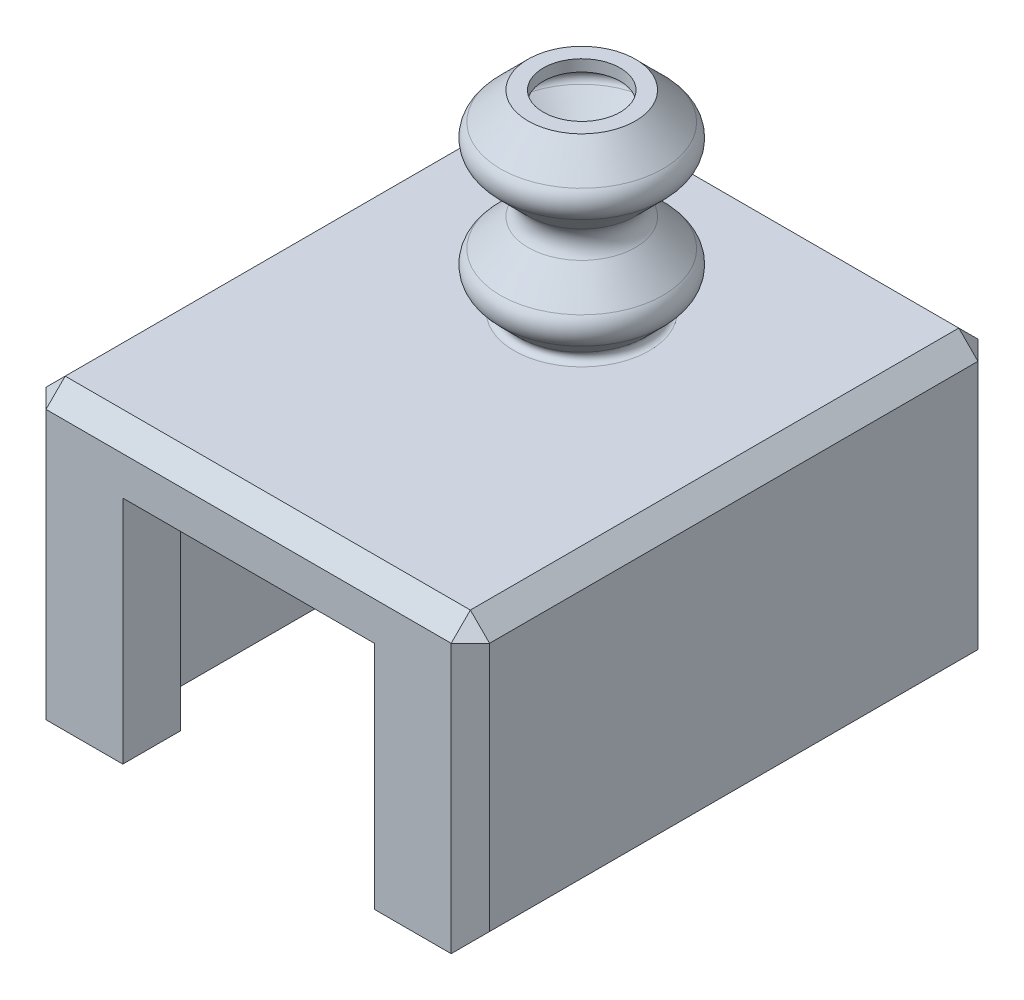
SolidWorks part; units mm, degrees
ref_plane "Front Plane" through (0, 0, 0) normal (0, 0, 1) x (1, 0, 0)
ref_plane "Top Plane" through (0, 0, 0) normal (0, 1, 0) x (1, 0, 0)
ref_plane "Right Plane" through (0, 0, 0) normal (1, 0, 0) x (0, 0, -1)
ref_axis "X Axis" through (-88.99, 0, 0) along (1, 0, 0)
ref_axis "Y Axis" through (0, 55, 0) along (0, -1, 0)
ref_axis "Z Axis" through (0, 0, -88.99) along (0, 0, 1)
sketch "Sketch1" plane through (0, 0, 0) normal (0, 0, 1) x (1, 0, 0)
  line L0 (0, 0) -> (2.7929, 0)
  line L1 (4.2322, 2.8536) -> (2.7929, 4.2929)
  line L2 (2.7929, 5.7071) -> (4.2322, 7.1464)
  line L3 (2.7929, 10) -> (0, 10)
  line L4 (0, 10) -> (0, 0) construction
  line L9 (0, 10) -> (0, 9.4)
  line L10 (0, 0.6) -> (0, 0)
  line L16 (4.2322, 8.5607) -> (2.7929, 10)
  line L17 (4.2322, 1.4393) -> (2.7929, 0)
  line L18 (3.5, 5) -> (0, 5) construction
  line L19 (0, 0.6) -> (2.5444, 0.6)
  line L20 (3.808, 1.8636) -> (2.5444, 0.6)
  line L21 (3.808, 2.4293) -> (2.3686, 3.8686)
  line L22 (2.3686, 6.1314) -> (3.808, 7.5707)
  line L23 (3.808, 8.1364) -> (2.5444, 9.4)
  line L24 (2.5444, 9.4) -> (0, 9.4)
  arc A0 (2.7929, 5.7071) -> (2.7929, 4.2929) centre (3.5, 5) ccw
  arc A1 (4.2322, 1.4393) -> (4.2322, 2.8536) centre (3.5251, 2.1464) ccw
  arc A2 (4.2322, 7.1464) -> (4.2322, 8.5607) centre (3.5251, 7.8536) ccw
  arc A3 (3.808, 1.8636) -> (3.808, 2.4293) centre (3.5251, 2.1464) ccw
  arc A4 (2.3686, 6.1314) -> (2.3686, 3.8686) centre (3.5, 5) ccw
  arc A5 (3.808, 7.5707) -> (3.808, 8.1364) centre (3.5251, 7.8536) ccw
  point P1 (2.7929, 5.7071)
  point P5 (2.7929, 4.2929)
  point P14 (2.7929, 4.2929)
  point P15 (2.7929, 4.2929)
  point P21 (0, 0)
  point P22 (0, 0)
  dimension "D3" = 1
  dimension "D4" = 1.9
  dimension "D1" = 5
  dimension "D2" = 10
  dimension "D5" = 0.6
revolve "Revolve1" add sketch "Sketch1" angle 360 about L4 region at (0.1098, 0.3, 0)
sketch "Sketch2" plane through (0, 10, 0) normal (0, 1, 0) x (1, 0, 0)
  circle A0 centre (0, 0) radius 2
  dimension "D1" = 4
extrude "Cut-Extrude1" cut sketch "Sketch2" against normal up to next
sketch "Sketch3" plane through (0, 0, 0) normal (0, -1, 0) x (1, 0, 0)
  line L0 (0, 0) -> (0, -2.75) construction
  line L5 (-8.55, 14.35) -> (8.55, 14.35)
  line L6 (-8.55, 14.35) -> (-8.55, -2.75)
  line L7 (-8.55, -2.75) -> (8.55, -2.75)
  line L8 (8.55, 14.35) -> (8.55, -2.75)
  line L9 (-11.55, 17.35) -> (-11.55, -10.0858)
  line L15 (11.55, 17.35) -> (11.55, -10.0858)
  line L16 (-11.55, 17.35) -> (11.55, 17.35)
  line L17 (-11.55, -5.75) -> (11.55, -5.75) construction
  line L18 (-11.55, -10.0858) -> (11.55, -10.0858)
  line L19 (-11.55, 0) -> (11.55, 0) construction
  line L20 (-11.55, 17.35) -> (-11.55, -5.75) construction
  line L21 (11.55, 17.35) -> (11.55, -5.75) construction
  circle A0 centre (0, 0) radius 2
  circle A2 centre (0, 0) radius 7.0858 construction
  point P14 (11.0854, -17.2755)
  point P17 (-11.0864, -5.3364)
  point P20 (-10.5801, -16.7702)
  dimension "D3" = 4
  dimension "D1" = 2.75
  dimension "D2" = 17.1
  dimension "D4" = 3
  dimension "D5" = 3
extrude "Boss-Extrude1" add sketch "Sketch3" along normal blind 15 contours L9 L18 L15 L16 L5 L8 L7 L6 | L7 region at (0, 0, 16.9913)
sketch "Sketch4" plane through (0, 0, 0) normal (0, 1, 0) x (1, 0, 0)
  line L4 (-11.55, 10.0858) -> (-11.55, -17.35)
  line L5 (-11.55, -17.35) -> (11.55, -17.35)
  line L6 (11.55, -17.35) -> (11.55, 10.0858)
  line L7 (11.55, 10.0858) -> (-11.55, 10.0858)
  line L8 (-11.55, 10.0858) -> (-11.55, -17.35)
  line L9 (-11.55, -17.35) -> (11.55, -17.35)
  line L10 (11.55, -17.35) -> (11.55, 10.0858)
  line L11 (11.55, 10.0858) -> (-11.55, 10.0858)
  dimension "D1" = 0
extrude "Boss-Extrude3" add sketch "Sketch4" against normal blind 1
fillet "Fillet2" radius 0.3 1 edges at (0, 0, 2.7929)
sketch "Sketch5" plane through (0, -1, 0) normal (0, 1, 0) x (1, 0, 0)
  circle A1 centre (0, 0) radius 2.7929 construction
  circle A2 centre (0, 0) radius 2.7929
  point P4 (0, 0)
  point P7 (-2.5341, 2.7929)
  point P10 (0, 0)
extrude "Cut-Extrude2" cut sketch "Sketch5" along normal up to next
sketch "Sketch6" plane through (0, -15, 0) normal (0, -1, 0) x (1, 0, 0)
  line L0 (-11.55, 17.35) -> (11.55, 17.35) construction
  line L1 (-6.55, 17.35) -> (6.55, 17.35)
  line L2 (-6.55, 17.35) -> (-6.55, 14.35)
  line L3 (-6.55, 14.35) -> (6.55, 14.35)
  line L4 (6.55, 17.35) -> (6.55, 14.35)
  line L5 (8.55, 14.35) -> (-8.55, 14.35) construction
  line L6 (0, 14.35) -> (0, 0) construction
  line L7 (-8.55, -2.75) -> (-8.55, 14.35) construction
  point P13 (0, 0)
  point P14 (0, 0)
  dimension "D1" = 2
extrude "Cut-Extrude3" cut sketch "Sketch6" against normal offset from surface (12 mm away) 2 contours L2 L1 L4 L3 up to face at (0, -1, 3.8738)
chamfer "Chamfer1" distance 1 angle 45 11 edges at (-11.55, -7.5, 17.35) (-11.55, -15, 3.6321) (-11.55, -7.5, -10.0858) (0, -15, -10.0858) (11.55, -7.5, -10.0858) (11.55, -15, 3.6321) (11.55, -7.5, 17.35) (0, 0, -10.0858) (11.55, 0, 3.6321) (0, 0, 17.35) (-11.55, 0, 3.6321)
equation "\"D5@Sketch3\"=\"D4@Sketch3\""
